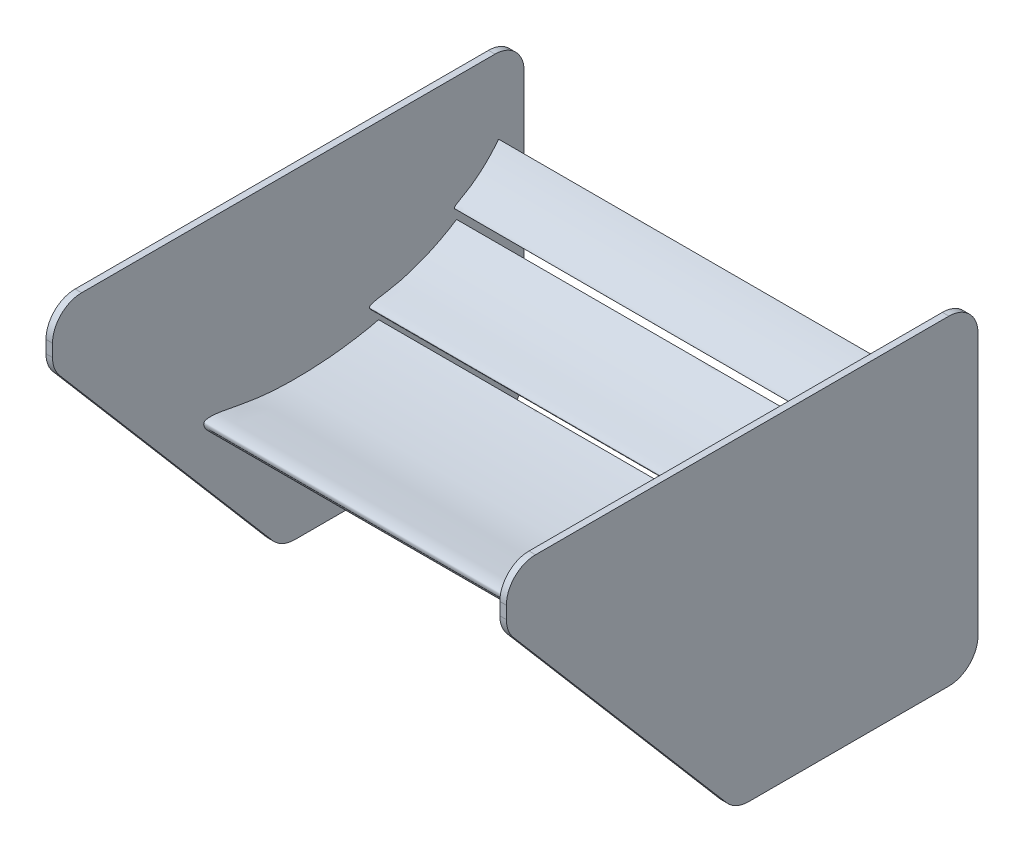
SolidWorks part; units mm, degrees
ref_plane "Front Plane" through (0, 0, 0) normal (0, 0, 1) x (1, 0, 0)
ref_plane "Top Plane" through (0, 0, 0) normal (0, 1, 0) x (1, 0, 0)
ref_plane "Right Plane" through (0, 0, 0) normal (1, 0, 0) x (0, 0, -1)
ref_plane "Soft Top Limit" through (0, 1174.6, 0) normal (0, 1, 0) x (1, 0, 0)
ref_plane "Soft Rear Limit" through (0, 0, -1192.975) normal (0, 0, 1) x (1, 0, 0)
ref_plane "Soft Right Limit" through (-501.65, 0, 0) normal (1, 0, 0) x (0, 0, -1)
ref_plane "Soft Left Limit" through (501.65, 0, 0) normal (1, 0, 0) x (0, 0, -1)
ref_plane "Soft Front Limit" through (0, 0, -165.1) normal (0, 0, 1) x (1, 0, 0)
ref_plane "Slant Limit" through (0, 528.6251, -619.2711) normal (0, -0.6492, 0.7606) x (1, 0, 0)
ref_plane "Bottom" through (0, 476.25, 0) normal (0, 1, 0) x (1, 0, 0)
ref_plane "Midplane" through (0, 0, 0) normal (1, 0, 0) x (0, 0, -1)
curve "Imported Airfoil Curve"
  spline degree 3 poles (0, 2520.0207, 6.126) (0, 2544.889, -1.81) (0, 2521.8965, 7.8839) (0, 2505.3253, 17.7145) (0, 2467.7144, 38.5723) (0, 2424.2142, 62.3813) (0, 2368.0949, 87.8078) (0, 2301.3729, 113.3478) (0, 2223.8362, 140.5377) (0, 2136.6129, 169.2441) (0, 2040.932, 199.097) (0, 1938.2341, 229.6055) (0, 1829.9414, 260.0781) (0, 1717.5266, 289.8586) (0, 1602.4273, 318.1375) (0, 1486.0259, 343.9752) (0, 1369.6902, 366.5754) (0, 1254.3666, 384.7865) (0, 1140.5393, 397.0034) (0, 1028.6357, 403.0127) (0, 919.0585, 402.9406) (0, 812.3986, 397.0375) (0, 709.2785, 385.5985) (0, 610.4299, 369.039) (0, 516.5862, 348.1086) (0, 428.5874, 323.3415) (0, 347.2653, 295.2055) (0, 273.332, 264.2656) (0, 207.4209, 231.0894) (0, 150.0337, 196.3024) (0, 101.596, 160.572) (0, 62.3674, 124.65) (0, 32.4977, 89.3959) (0, 12.0597, 55.6746) (0, 1.683, 26.6201) (0, -0.5567, 6.5526) (0, 0.5894, -3.9947) (0, 1.6947, -9.1451) (0, 2.8711, -12.4915) (0, 3.9449, -14.9776) (0, 4.8993, -16.669) (0, 5.9763, -18.2433) (0, 7.3264, -19.6365) (0, 8.8595, -20.9434) (0, 11.1868, -22.7306) (0, 14.6073, -24.7406) (0, 20.085, -27.4067) (0, 26.8353, -29.9257) (0, 44.6446, -35.1819) (0, 77.8093, -38.8998) (0, 130.2841, -38.2927) (0, 196.3018, -31.4611) (0, 276.2192, -18.4434) (0, 370.8288, 0.8611) (0, 480.7331, 24.811) (0, 605.9792, 50.0099) (0, 745.0759, 74.1542) (0, 895.4497, 95.0846) (0, 1053.6786, 110.004) (0, 1215.6439, 118.3392) (0, 1377.6893, 121.6348) (0, 1537.1174, 120.5125) (0, 1691.5141, 115.2051) (0, 1838.3121, 105.7388) (0, 1975.028, 93.0069) (0, 2099.5942, 78.4581) (0, 2210.5746, 63.1262) (0, 2306.3634, 48.0168) (0, 2387.2069, 33.7158) (0, 2449.0745, 22.0129) (0, 2499.1865, 10.4993) (0, 2520.0207, 6.126) (0, 2544.889, -1.81) (0, 2521.8965, 7.8839) knots -0.016237 -0.007308 -0.001841 0 0.001813 0.006911 0.014576 0.024172 0.035572 0.049013 0.064513 0.081849 0.100772 0.120997 0.142228 0.164173 0.186537 0.209023 0.231367 0.25332 0.274804 0.295858 0.316449 0.336531 0.356033 0.374893 0.39299 0.410197 0.426388 0.441459 0.455334 0.467938 0.479236 0.489204 0.497851 0.505194 0.511308 0.515097 0.516441 0.517273 0.51806 0.518436 0.518797 0.519154 0.519508 0.519887 0.520289 0.52116 0.522116 0.52372 0.525214 0.532575 0.542381 0.554776 0.569931 0.588005 0.609188 0.633329 0.660001 0.688743 0.718873 0.749543 0.780127 0.810209 0.839387 0.867183 0.893104 0.91676 0.937874 0.956199 0.971544 0.983763 0.992692 0.998159 1 1.001813 1.006911 1.014576 periodic
sketch "Airfoils Sketch" plane through (0, 0, 0) normal (1, 0, 0) x (0, 0, -1)
  line L0 (165.1, 1174.6) -> (165.1, 1060.6753) construction
  line L1 (165.1, 1060.6753) -> (663.9798, 476.25) construction
  line L2 (663.9798, 476.25) -> (1192.975, 476.25) construction
  line L3 (1192.975, 476.25) -> (1192.975, 1174.6) construction
  line L4 (1192.975, 1174.6) -> (165.1, 1174.6) construction
  line L5 (509.9361, 1174.6) -> (-509.9361, 1174.6) construction
  line L6 (165.1, 67.0076) -> (165.1, -67.0076) construction
  line L7 (364.7288, 826.8151) -> (873.8134, 230.4351) construction
  line L8 (279.3831, 476.25) -> (-279.3831, 476.25) construction
  line L9 (1192.975, 353.2696) -> (1192.975, -353.2696) construction
  line L10 (502.3839, 352.3587) -> (486.9801, 1234.8413) construction
  line L11 (883.1435, 369.455) -> (868.1045, 1231.0438) construction
  line L12 (875.624, 800.2494) -> (494.682, 793.6) construction
  line L13 (393.082, 793.6) -> (1192.975, 793.6) construction
  line L14 (834.2182, 888.0761) -> (877.4997, 775.3239) construction
  line L15 (1023.7202, 961.4213) -> (1067.4047, 847.6194) construction
  line L16 (1045.5625, 904.5204) -> (855.8589, 831.7) construction
  line L17 (360.5589, 831.7) -> (1192.975, 831.7) construction
  line L18 (1012.8055, 959.673) -> (1069.6968, 894.227) construction
  line L19 (1118.0222, 1032.2151) -> (1156.1764, 988.3238) construction
  line L20 (1137.108, 1010.277) -> (1041.2512, 926.95) construction
  line L21 (279.2512, 926.95) -> (1192.975, 926.95) construction
  spline S0 degree 3 poles (872.6415, 799.2849) (876.3531, 800.532) (872.9268, 799.0256) (870.464, 797.5133) (864.8707, 794.2991) (858.4009, 790.6288) (850.0422, 786.6871) (840.0936, 782.7042) (828.5267, 778.449) (815.5105, 773.9443) (801.2285, 769.2484) (785.8955, 764.438) (769.7234, 759.6203) (752.9314, 754.8969) (735.7334, 750.3927) (718.3345, 746.2515) (700.938, 742.5961) (683.6833, 739.6013) (666.6394, 737.5089) (649.8698, 736.3519) (633.4352, 736.1124) (617.4248, 736.754) (601.9327, 738.234) (587.0695, 740.4918) (572.9469, 743.4165) (559.6922, 746.93) (547.4312, 750.964) (536.272, 755.4355) (526.3108, 760.2607) (517.6243, 765.3469) (510.278, 770.5951) (504.3124, 775.893) (499.752, 781.1122) (496.6096, 786.1231) (494.9869, 790.4569) (494.6052, 793.4616) (494.7529, 795.0461) (494.907, 795.8211) (495.0757, 796.3256) (495.2311, 796.701) (495.3704, 796.9568) (495.5283, 797.1954) (495.7276, 797.4074) (495.9546, 797.6069) (496.2995, 797.8803) (496.808, 798.1896) (497.6234, 798.602) (498.6301, 798.9952) (501.2891, 799.8242) (506.2547, 800.4576) (514.1263, 800.4865) (524.0432, 799.6127) (536.059, 797.8429) (550.2927, 795.1638) (566.8309, 791.8229) (585.673, 788.3297) (606.5899, 785.0264) (629.1909, 782.2308) (652.9562, 780.3548) (677.2669, 779.4747) (701.5781, 779.3507) (725.4866, 779.8833) (748.6309, 781.0321) (770.6262, 782.7873) (791.1018, 785.0092) (809.751, 787.4759) (826.3609, 790.029) (840.6928, 792.5139) (852.7851, 794.8435) (862.0372, 796.7401) (869.5268, 798.5814) (872.6415, 799.2849) (876.3531, 800.532) (872.9268, 799.0256) knots -0.016237 -0.007308 -0.001841 0 0.001813 0.006911 0.014576 0.024172 0.035572 0.049013 0.064513 0.081849 0.100772 0.120997 0.142228 0.164173 0.186537 0.209023 0.231367 0.25332 0.274804 0.295858 0.316449 0.336531 0.356033 0.374893 0.39299 0.410197 0.426388 0.441459 0.455334 0.467938 0.479236 0.489204 0.497851 0.505194 0.511308 0.515097 0.516441 0.517273 0.51806 0.518436 0.518797 0.519154 0.519508 0.519887 0.520289 0.52116 0.522116 0.52372 0.525214 0.532575 0.542381 0.554776 0.569931 0.588005 0.609188 0.633329 0.660001 0.688743 0.718873 0.749543 0.780127 0.810209 0.839387 0.867183 0.893104 0.91676 0.937874 0.956199 0.971544 0.983763 0.992692 0.998159 1 1.001813 1.006911 1.014576 only from (875.624, 800.2494) to (875.624, 800.2494)
  spline S1 degree 3 poles (1044.2437, 903.493) (1045.8763, 904.795) (1044.434, 903.415) (1043.4755, 902.2079) (1041.2586, 899.5768) (1038.6857, 896.5572) (1035.2156, 893.057) (1030.9562, 889.2461) (1025.9354, 885.0037) (1020.2338, 880.3718) (1013.9326, 875.4131) (1007.1257, 870.2054) (999.8995, 864.8409) (992.3455, 859.4107) (984.548, 854.0162) (976.5836, 848.767) (968.5318, 843.7617) (960.4305, 839.1134) (952.2703, 834.9557) (944.0769, 831.3169) (935.8841, 828.199) (927.7432, 825.6001) (919.709, 823.5159) (911.8482, 821.9362) (904.2369, 820.8259) (896.9532, 820.169) (890.0725, 819.9542) (883.6642, 820.1596) (877.7917, 820.7608) (872.5106, 821.7253) (867.8715, 823.0155) (863.9153, 824.5825) (860.6777, 826.3663) (858.1889, 828.3044) (856.5851, 830.1804) (855.8457, 831.6166) (855.6307, 832.4377) (855.5665, 832.8542) (855.5591, 833.1378) (855.5685, 833.3543) (855.5916, 833.5079) (855.6272, 833.6563) (855.6884, 833.7989) (855.7658, 833.9403) (855.8888, 834.1402) (856.0872, 834.388) (856.4206, 834.7434) (856.8534, 835.1241) (858.0348, 836.0246) (860.4079, 837.2478) (864.3476, 838.6981) (869.4771, 840.0692) (875.8219, 841.374) (883.4441, 842.6277) (892.3419, 843.9701) (902.4222, 845.6564) (913.5077, 847.8164) (925.3445, 850.538) (937.5972, 853.9328) (949.9415, 857.9263) (962.1481, 862.2987) (974.0332, 866.9268) (985.4229, 871.7244) (996.126, 876.6162) (1005.9825, 881.4647) (1014.879, 886.1027) (1022.7376, 890.4121) (1029.467, 894.2718) (1035.1024, 897.6451) (1039.3933, 900.2833) (1042.811, 902.5722) (1044.2437, 903.493) (1045.8763, 904.795) (1044.434, 903.415) knots -0.016237 -0.007308 -0.001841 0 0.001813 0.006911 0.014576 0.024172 0.035572 0.049013 0.064513 0.081849 0.100772 0.120997 0.142228 0.164173 0.186537 0.209023 0.231367 0.25332 0.274804 0.295858 0.316449 0.336531 0.356033 0.374893 0.39299 0.410197 0.426388 0.441459 0.455334 0.467938 0.479236 0.489204 0.497851 0.505194 0.511308 0.515097 0.516441 0.517273 0.51806 0.518436 0.518797 0.519154 0.519508 0.519887 0.520289 0.52116 0.522116 0.52372 0.525214 0.532575 0.542381 0.554776 0.569931 0.588005 0.609188 0.633329 0.660001 0.688743 0.718873 0.749543 0.780127 0.810209 0.839387 0.867183 0.893104 0.91676 0.937874 0.956199 0.971544 0.983763 0.992692 0.998159 1 1.001813 1.006911 1.014576 only from (1045.5625, 904.5204) to (1045.5625, 904.5204)
  spline S2 degree 3 poles (1136.553, 1009.3917) (1137.2336, 1010.5054) (1136.6814, 1009.3866) (1136.3765, 1008.4726) (1135.6369, 1006.4533) (1134.7712, 1004.1296) (1133.4813, 1001.3319) (1131.7941, 998.183) (1129.7521, 994.6178) (1127.3934, 990.6783) (1124.7524, 986.4187) (1121.8676, 981.9047) (1118.7701, 977.2089) (1115.494, 972.4045) (1112.0673, 967.569) (1108.5115, 962.7832) (1104.8522, 958.122) (1101.0876, 953.6599) (1097.1835, 949.4733) (1093.1489, 945.5844) (1089.0033, 942.0016) (1084.7772, 938.7347) (1080.5038, 935.793) (1076.2244, 933.1846) (1071.9912, 930.9053) (1067.8535, 928.9623) (1063.8579, 927.3652) (1060.05, 926.1159) (1056.4723, 925.2136) (1053.1641, 924.6511) (1050.1635, 924.4171) (1047.5048, 924.4918) (1045.2218, 924.8474) (1043.3456, 925.4536) (1042.0025, 926.2127) (1041.2612, 926.8982) (1040.9594, 927.3345) (1040.8327, 927.5654) (1040.7677, 927.7304) (1040.7269, 927.8596) (1040.7077, 927.9547) (1040.6969, 928.0495) (1040.7023, 928.1464) (1040.7175, 928.2459) (1040.7471, 928.3897) (1040.8106, 928.5776) (1040.9305, 928.8576) (1041.1033, 929.1738) (1041.6047, 929.9553) (1042.737, 931.181) (1044.741, 932.8751) (1047.4608, 934.777) (1050.9085, 936.8999) (1055.1175, 939.2657) (1060.0567, 941.9564) (1065.617, 945.1018) (1071.6664, 948.7404) (1078.0371, 952.8695) (1084.5081, 957.4828) (1090.9049, 962.4674) (1097.1398, 967.6452) (1103.1313, 972.9044) (1108.7955, 978.1572) (1114.0363, 983.3186) (1118.7891, 988.2736) (1123.023, 992.8997) (1126.7176, 997.1108) (1129.8451, 1000.8165) (1132.4339, 1004.0026) (1134.3903, 1006.4695) (1135.9083, 1008.5446) (1136.553, 1009.3917) (1137.2336, 1010.5054) (1136.6814, 1009.3866) knots -0.016237 -0.007308 -0.001841 0 0.001813 0.006911 0.014576 0.024172 0.035572 0.049013 0.064513 0.081849 0.100772 0.120997 0.142228 0.164173 0.186537 0.209023 0.231367 0.25332 0.274804 0.295858 0.316449 0.336531 0.356033 0.374893 0.39299 0.410197 0.426388 0.441459 0.455334 0.467938 0.479236 0.489204 0.497851 0.505194 0.511308 0.515097 0.516441 0.517273 0.51806 0.518436 0.518797 0.519154 0.519508 0.519887 0.520289 0.52116 0.522116 0.52372 0.525214 0.532575 0.542381 0.554776 0.569931 0.588005 0.609188 0.633329 0.660001 0.688743 0.718873 0.749543 0.780127 0.810209 0.839387 0.867183 0.893104 0.91676 0.937874 0.956199 0.971544 0.983763 0.992692 0.998159 1 1.001813 1.006911 1.014576 only from (1137.108, 1010.277) to (1137.108, 1010.277)
  point P36 (494.682, 352.3587)
  point P38 (877.4997, 369.455)
  dimension "D1" = 381
  dimension "D2" = 381
  dimension "D3" = 1
  dimension "D4" = 101.6
  dimension "D5" = 203.2
  dimension "D6" = 342.9
  dimension "D7" = 21
  dimension "D8" = 495.3
  dimension "D9" = 127
  dimension "D10" = 247.65
  dimension "D11" = 41
  dimension "D12" = 762
extrude "Extruded Airfoils" add sketch "Airfoils Sketch" along normal offset from surface (487.45 mm away) 14.2 up to plane "Soft Left Limit"
sketch "Endplate Sketch" plane through (501.65, 0, 0) normal (1, 0, 0) x (0, 0, -1)
  line L0 (228.6, 1174.6) -> (1129.475, 1174.6)
  line L1 (1192.975, 1111.1) -> (1192.975, 539.75)
  line L2 (1129.475, 476.25) -> (693.2639, 476.25)
  line L3 (644.9672, 498.5228) -> (180.3033, 1042.8649)
  line L4 (165.1, 1084.0921) -> (165.1, 1111.1)
  line L5 (165.1, 67.0076) -> (165.1, -67.0076) construction
  line L6 (509.9361, 1174.6) -> (-509.9361, 1174.6) construction
  line L7 (1192.975, 353.2696) -> (1192.975, -353.2696) construction
  line L8 (279.3831, 476.25) -> (-279.3831, 476.25) construction
  line L9 (364.7288, 826.8151) -> (873.8134, 230.4351) construction
  arc A0 (1129.475, 1174.6) -> (1192.975, 1111.1) centre (1129.475, 1111.1) cw
  arc A1 (1192.975, 539.75) -> (1129.475, 476.25) centre (1129.475, 539.75) cw
  arc A2 (693.2639, 476.25) -> (644.9672, 498.5228) centre (693.2639, 539.75) cw
  arc A3 (180.3033, 1042.8649) -> (165.1, 1084.0921) centre (228.6, 1084.0921) cw
  arc A4 (228.6, 1174.6) -> (165.1, 1111.1) centre (228.6, 1111.1) ccw
  dimension "D1" = 63.5
extrude "Extruded Endplate" add sketch "Endplate Sketch" against normal up to surface (14.2 mm away)
mirror "Mirror" about plane through (0, 0, 0) normal (1, 0, 0) of bodies 106
